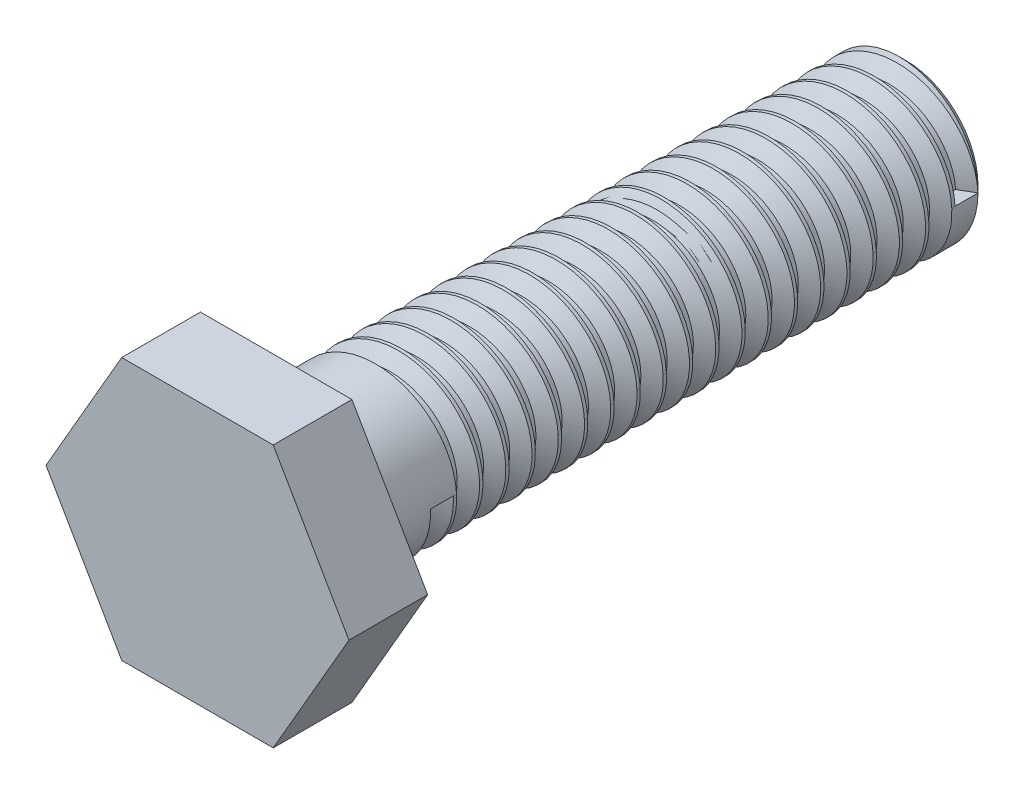
SolidWorks part; units mm, degrees
material "AISI 1018"
ref_plane "Front Plane" through (0, 0, 0) normal (0, 0, 1) x (1, 0, 0)
ref_plane "Top Plane" through (0, 0, 0) normal (0, 1, 0) x (1, 0, 0)
ref_plane "Right Plane" through (0, 0, 0) normal (1, 0, 0) x (0, 0, -1)
ref_plane "Plane1"
sketch "Sketch1" plane through (0, 0, 0) normal (0, 0, 1) x (1, 0, 0)
  line L0 (6.9282, -4) -> (4.6188, -8)
  line L1 (4.6188, -8) -> (0, -8)
  line L2 (0, -8) -> (-4.6188, -8)
  line L3 (-4.6188, -8) -> (-6.9282, -4)
  line L4 (-6.9282, -4) -> (-9.2376, 0)
  line L5 (-9.2376, 0) -> (-6.9282, 4)
  line L6 (-6.9282, 4) -> (-4.6188, 8)
  line L7 (-4.6188, 8) -> (0, 8)
  line L8 (0, 8) -> (4.6188, 8)
  line L9 (4.6188, 8) -> (6.9282, 4)
  line L10 (6.9282, 4) -> (9.2376, 0)
  line L11 (9.2376, 0) -> (6.9282, -4)
extrude "Extrusion1" add sketch "Sketch1" against normal blind 5.8
sketch "Sketch2" plane through (0, 0, -5.8) normal (0, 0, -1) x (-1, 0, 0)
  circle A0 centre (0, 0) radius 3
  dimension "D1" = 6
extrude "Extrusion2" add sketch "Sketch2" along normal blind 4
cosmetic thread "Cosmetic Thread1" parameters "D2"=0
sketch "Sketch3" plane through (0, 0, 0) normal (0, 0, 1) x (1, 0, 0)
  line L0 (4.6188, -8) -> (9.2376, 0)
  line L1 (9.2376, 0) -> (4.6188, 8)
  line L2 (4.6188, 8) -> (-4.6188, 8)
  line L3 (-4.6188, 8) -> (-9.2376, 0)
  line L4 (-9.2376, 0) -> (-4.6188, -8)
  line L5 (-4.6188, -8) -> (4.6188, -8)
  line L6 (5.7735, 0) -> (2.8868, -5)
  line L7 (2.8868, -5) -> (-2.8868, -5)
  line L8 (-2.8868, -5) -> (-5.7735, 0)
  line L9 (-5.7735, 0) -> (-2.8868, 5)
  line L10 (-2.8868, 5) -> (2.8868, 5)
  line L11 (2.8868, 5) -> (5.7735, 0)
  line M1 (4.6188, -8) -> (9.2376, 0)
  line M2 (9.2376, 0) -> (4.6188, 8)
  line M3 (4.6188, 8) -> (-4.6188, 8)
  line M4 (-4.6188, 8) -> (-9.2376, 0)
  line M5 (-9.2376, 0) -> (-4.6188, -8)
  line M6 (-4.6188, -8) -> (4.6188, -8)
extrude "Extrusion4" cut sketch "Sketch3" against normal blind 10 contours L10 L11 L6 L7 L8 L9 M6 M1 M2 M3 M4 M5
sketch "Sketch4" plane through (0, 0, -9.8) normal (0, 0, -1) x (-1, 0, 0)
  circle A0 centre (0, 0) radius 3
  dimension "D1" = 6
extrude "Thread2" add sketch "Sketch4" along normal blind 20
chamfer "Chamfer2" distance 0.25 distance2 0.25 1 edges at (-3, 0, -29.8)
sketch "Sketch5" plane through (0, 0, 0) normal (0, 0, 1) x (1, 0, 0)
  line L0 (5.7735, 0) -> (2.8868, 5)
  line L1 (2.8868, 5) -> (-2.8868, 5)
  line L2 (-2.8868, 5) -> (-5.7735, 0)
  line L3 (-5.7735, 0) -> (-2.8868, -5)
  line L4 (-2.8868, -5) -> (2.8868, -5)
  line L5 (2.8868, -5) -> (5.7735, 0)
extrude "Extrusion6" cut sketch "Sketch5" against normal blind 2.8
thread "Thread3" pitch 1 start angle 0, offset 0, length 20, pitch 1, diameter 6
ref_plane "Plane2" through (3, 0, -29.55) normal (0, -1, 0) x (1, 0, 0)
sketch "Thread Profile1" plane through (3, 0, -29.55) normal (0, -1, 0) x (1, 0, 0)
  line L0 (0, 0) -> (0, 1) construction
  line L11 (0, 0) -> (0, 0.875)
  line L12 (0, 0.875) -> (-0.5413, 0.5625)
  line L13 (-0.5413, 0.5625) -> (-0.5413, 0.3125)
  line L15 (-0.5413, 0.3125) -> (0, 0)
  line L17 (-0.5413, 0.4375) -> (0, 0.4375) construction
  point P2 (0, 0)
  dimension "Pitch" = 1
  dimension "Profile_Angle" = 60
  dimension "Profile_Land" = 0.25
  dimension "Profile_Height" = 0.5413
